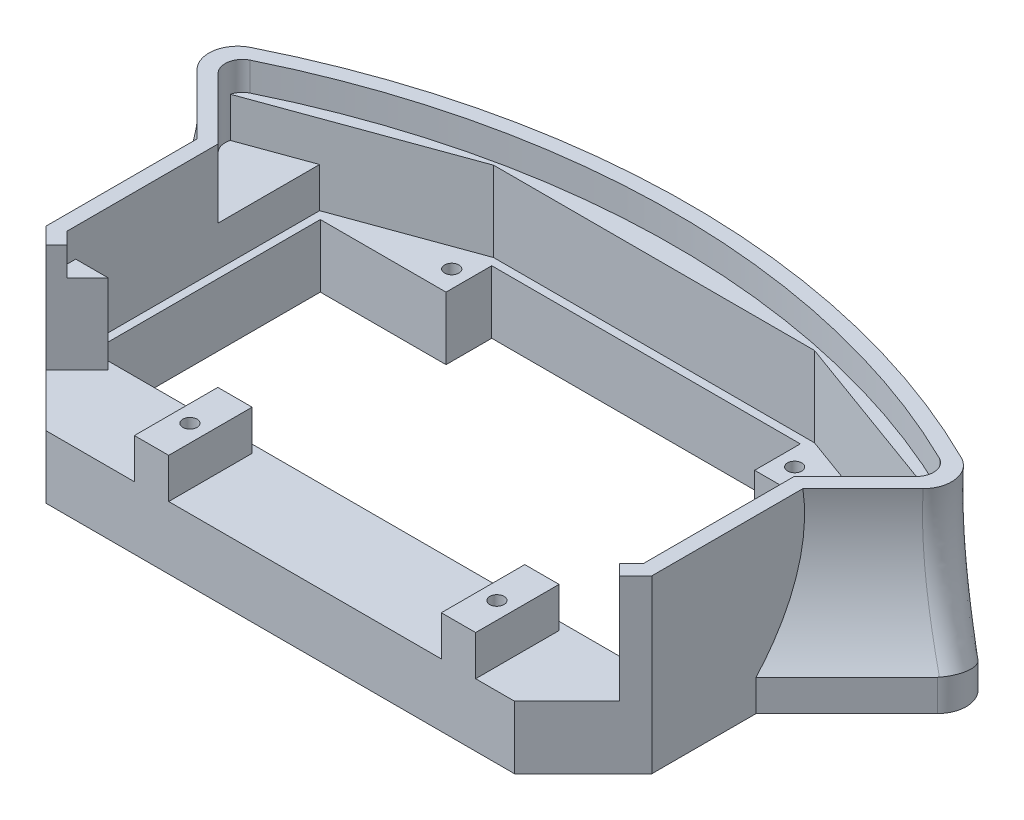
SolidWorks part; units mm, degrees
material "ABS"
ref_plane "Front Plane" through (0, 0, 0) normal (0, 0, 1) x (1, 0, 0)
ref_plane "Top Plane" through (0, 0, 0) normal (0, 1, 0) x (1, 0, 0)
ref_plane "Right Plane" through (0, 0, 0) normal (1, 0, 0) x (0, 0, -1)
sketch "Sketch1" plane through (0, 0, 0) normal (0, 1, 0) x (1, 0, 0)
  line L0 (53, 80) -> (53, 129.1478)
  line L1 (-53, 129.1478) -> (-53, 80)
  line L2 (-41, 68) -> (41, 68)
  line L3 (-53, 80) -> (-41, 68)
  line L4 (41, 68) -> (53, 80)
  circle A0 centre (0, 0) radius 140 construction
  arc A1 (53, 129.1478) -> (-53, 129.1478) centre (0, 0) ccw
  dimension "D1" = 280
  dimension "D3" = 139.6
  dimension "D2" = 106
  dimension "D4" = 68
  dimension "D5" = 80
  dimension "D6" = 135
  dimension "D7" = 135
extrude "Boss-Extrude1" add sketch "Sketch1" along normal blind 30
sketch "Sketch2" plane through (0, 30, 0) normal (0, 1, 0) x (1, 0, 0)
  line L0 (-49, 84) -> (49, 84)
  line L1 (49, 84) -> (49, 124)
  line L2 (49, 124) -> (27, 124)
  line L3 (27, 124) -> (27, 132)
  line L4 (27, 132) -> (-27, 132)
  line L5 (-27, 132) -> (-27, 124)
  line L6 (-27, 124) -> (-49, 124)
  line L7 (-49, 124) -> (-49, 84)
  line L12 (-53, 129.1478) -> (-53, 80) construction
  dimension "D1" = 48
  dimension "D2" = 98
  dimension "D3" = 8
  dimension "D4" = 84
  dimension "D5" = 22
  dimension "D6" = 4
extrude "Cut-Extrude1" cut sketch "Sketch2" against normal up to next
sketch "Sketch3" plane through (0, 30, 0) normal (0, 1, 0) x (1, 0, 0)
  line L0 (-50, 83) -> (50, 83) construction
  line L1 (50, 83) -> (50, 125) construction
  line L2 (50, 125) -> (28, 133) construction
  line L3 (28, 133) -> (-28, 133) construction
  line L4 (-28, 133) -> (-50, 125) construction
  line L5 (-50, 125) -> (-50, 83) construction
  line L7 (-49, 84) -> (-49, 124) construction
  line L8 (-50.4, 125.2802) -> (-50.4, 82.6)
  line L9 (-50.4, 82.6) -> (50.4, 82.6)
  line L10 (50.4, 82.6) -> (50.4, 125.2802)
  line L11 (50.4, 125.2802) -> (28.0705, 133.4)
  line L12 (28.0705, 133.4) -> (-28.0705, 133.4)
  line L13 (-28.0705, 133.4) -> (-50.4, 125.2802)
  line L16 (-49, 84) -> (49, 84) construction
  dimension "D1" = 50
  dimension "D2" = 22
  dimension "D3" = 8
  dimension "D4" = 1
  dimension "D5" = 1
  dimension "D6" = 100
  dimension "D7" = 0.4
extrude "Cut-Extrude2" cut sketch "Sketch3" against normal offset from surface (19 mm away) 11 up to face at (0, 0, -116)
sketch "Sketch5" plane through (0, 30, 0) normal (0, 1, 0) x (1, 0, 0)
  line L1 (-37.48, 71.91) -> (43.8, 71.91) construction
  line L2 (-37.48, 71.91) -> (-37.48, 125.25) construction
  line L3 (-37.48, 125.25) -> (43.8, 125.25) construction
  line L4 (43.8, 71.91) -> (43.8, 125.25) construction
  line L6 (-37.88, 71.51) -> (-37.88, 125.65)
  line L7 (-37.88, 125.65) -> (44.2, 125.65)
  line L8 (44.2, 71.51) -> (44.2, 125.65)
  line L9 (-37.88, 71.51) -> (44.2, 71.51)
  dimension "D1" = 71.91
  dimension "D2" = 43.8
  dimension "D3" = 81.28
  dimension "D4" = 53.34
  dimension "D5" = 0.4
extrude "Cut-Extrude4" cut sketch "Sketch5" against normal offset from surface (12 mm away) 18 up to face at (0, 0, -116)
sketch "Sketch4" plane through (0, 18, 0) normal (0, 1, 0) x (1, 0, 0)
  circle A0 centre (31.18, 74.72) radius 1.25
  circle A1 centre (-22.53, 74.72) radius 1.25
  dimension "D2" = 2.5
  dimension "D1" = 22.53
  dimension "D3" = 5.28
  dimension "D4" = 53.71
extrude "Cut-Extrude3" cut sketch "Sketch4" against normal up to next
fillet "Fillet1" radius 6 2 edges at (44.2, 24, -71.51) (-37.88, 24, -71.51)
sketch "Sketch6" plane through (0, 30, 0) normal (0, 1, 0) x (1, 0, 0)
  line L20 (50.4, 81.077) -> (50.4, 127.3925)
  line L21 (39.923, 70.6) -> (50.4, 81.077)
  line L22 (-39.923, 70.6) -> (39.923, 70.6)
  line L23 (-50.4, 81.077) -> (-39.923, 70.6)
  line L24 (-50.4, 127.3925) -> (-50.4, 81.077)
  line L25 (50.4, 81.077) -> (50.4, 127.3925)
  line L26 (39.923, 70.6) -> (50.4, 81.077)
  line L27 (-39.923, 70.6) -> (39.923, 70.6)
  line L28 (-50.4, 81.077) -> (-39.923, 70.6)
  line L29 (-50.4, 127.3925) -> (-50.4, 81.077)
  arc A7 (50.4, 127.3925) -> (-50.4, 127.3925) centre (0, 0) ccw
  arc A8 (50.4, 127.3925) -> (-50.4, 127.3925) centre (0, 0) ccw
  dimension "D1" = 2.6
extrude "Cut-Extrude5" cut sketch "Sketch6" against normal blind 5
sketch "Sketch7" plane through (0, 0, 0) normal (0, -1, 0) x (1, 0, 0)
  line L0 (73.4563, -118.7111) -> (53, -98.2548)
  line L1 (53, -80) -> (53, -129.1478) construction
  line L2 (53, -98.2548) -> (53, -129.1478)
  line L3 (0, 0) -> (103.3995, -103.3995) construction
  arc A0 (53, -129.1478) -> (73.4563, -118.7111) centre (0, 0) ccw
  arc A1 (-53, -129.1478) -> (53, -129.1478) centre (0, 0) ccw construction
  dimension "D1" = 45
  dimension "D2" = 32
extrude "Boss-Extrude2" add sketch "Sketch7" against normal up to surface (30 mm away) up to face at (0, 30, -94.6244)
ref_plane "Plane1" through (96.0837, 0, -96.0837) normal (-0.7071, 0, 0.7071) x (0, -1, 0)
sketch "Sketch8" plane through (96.0837, 0, -96.0837) normal (-0.7071, 0, 0.7071) x (0, -1, 0)
  line L0 (-30, -32) -> (0, -32) construction
  circle A0 centre (-26, 0) radius 38
  dimension "D3" = 76
  dimension "D1" = 32
  dimension "D2" = 26
extrude "Cut-Extrude6" cut sketch "Sketch8" along normal up to surface (98.9296 mm away) up to face at (53, 18.75, -84.5637)
mirror "Mirror1" about plane through (0, 0, 0) normal (1, 0, 0) of "Boss-Extrude2"
ref_plane "Plane2" through (-96.0837, 0, -96.0837) normal (0.7071, 0, 0.7071) x (0, -1, 0)
sketch "Sketch9" plane through (-96.0837, 0, -96.0837) normal (0.7071, 0, 0.7071) x (0, -1, 0)
  line L0 (-30, 32) -> (0, 32) construction
  circle A0 centre (-26, 0) radius 38
  dimension "D1" = 76
  dimension "D2" = 32
  dimension "D3" = 26
extrude "Cut-Extrude7" cut sketch "Sketch9" along normal up to surface (22.9296 mm away) up to face at (-53, 18.75, -93.6911)
fillet "Fillet2" radius 5 4 edges at (69.0949, 16.9868, -121.3015) (73.4563, 2.753, -118.7111) (-73.4563, 2.753, -118.7111) (-68.9598, 17.6248, -121.3784)
sketch "Sketch11" plane through (0, 11, 0) normal (0, 1, 0) x (1, 0, 0)
  line L0 (-49, 124) -> (-27, 124) construction
  circle A0 centre (-30, 128) radius 1.25
  circle A1 centre (30, 128) radius 1.25
  dimension "D2" = 2.5
  dimension "D1" = 4
  dimension "D3" = 60
  dimension "D4" = 30
extrude "Cut-Extrude9" cut sketch "Sketch11" against normal up to next
sketch "Sketch12" plane through (0, 30, 0) normal (0, 1, 0) x (1, 0, 0)
  line L0 (-61.0884, 118.2069) -> (-50.4, 107.5185)
  line L1 (-50.4, 127.3925) -> (-50.4, 81.077) construction
  line L2 (-50.4, 107.5185) -> (-50.4, 127.3925)
  line L3 (-63.5251, 116.9667) -> (-53, 106.4416) construction
  arc A0 (-50.4, 127.3925) -> (-60.2872, 123.0221) centre (0, 0) ccw
  arc A1 (-60.2872, 123.0221) -> (-61.0884, 118.2069) centre (-58.9671, 120.3282) ccw
  arc A3 (62.1871, 124.9837) -> (-62.1871, 124.9837) centre (0, 0) ccw construction
  dimension "D1" = 2.6
  dimension "D2" = 3
extrude "Cut-Extrude10" cut sketch "Sketch12" against normal up to surface (12 mm away) up to face at (-22.53, 18, -73.47)
sketch "Sketch14" plane through (0, 18, 0) normal (0, 1, 0) x (1, 0, 0)
  line L0 (-50.4, 127.3925) -> (-61.8629, 123.2241)
  line L1 (-61.8629, 123.2241) -> (-61.8629, 121.1118)
  line L2 (-61.8629, 121.1118) -> (-50.4, 125.2802)
  line L3 (-50.4, 125.2802) -> (-50.4, 127.3925)
  line L4 (-50.4, 125.2802) -> (-28.0705, 133.4) construction
  arc A0 (-60.2872, 123.0221) -> (-61.0884, 118.2069) centre (-58.9671, 120.3282) ccw construction
extrude "Boss-Extrude3" add sketch "Sketch14" along normal up to surface (7 mm away) up to face at (0, 25, -130.2921)
mirror "Mirror2" about plane through (0, 0, 0) normal (1, 0, 0) of "Boss-Extrude3", "Cut-Extrude10"
sketch "Sketch15" plane through (0, 30, 0) normal (0, 1, 0) x (1, 0, 0)
  line L0 (-50.1716, 77.1716) -> (-43.3431, 84)
  line L1 (-53, 80) -> (-41, 68) construction
  line L2 (49, 84) -> (-49, 84) construction
  line L3 (-43.3431, 84) -> (43.3431, 84)
  line L4 (43.3431, 84) -> (50.1716, 77.1716)
  line L5 (41, 68) -> (53, 80) construction
  line L6 (50.1716, 77.1716) -> (41, 68)
  line L7 (41, 68) -> (-41, 68)
  line L8 (-41, 68) -> (-50.1716, 77.1716)
  dimension "D1" = 4
  dimension "D2" = 4
extrude "Cut-Extrude12" cut sketch "Sketch15" against normal up to surface (12 mm away) up to face at (-22.53, 18, -73.47)
sketch "Sketch16" plane through (0, 18, 0) normal (0, 1, 0) x (1, 0, 0)
  line L0 (-50.1716, 77.1716) -> (-44.7431, 82.6)
  line L1 (-44.7431, 82.6) -> (-25.53, 82.6)
  line L2 (50.4, 82.6) -> (-50.4, 82.6) construction
  line L3 (-25.53, 82.6) -> (-25.53, 68)
  line L4 (41, 68) -> (-41, 68) construction
  line L5 (-25.53, 68) -> (-41, 68)
  line L6 (-41, 68) -> (-50.1716, 77.1716) construction
  line L7 (-41, 68) -> (-50.1716, 77.1716)
  line L8 (44.7431, 82.6) -> (-44.7431, 82.6) construction
  line L9 (-19.53, 68) -> (28.18, 68)
  line L10 (-19.53, 68) -> (-19.53, 82.6)
  line L11 (-19.53, 82.6) -> (28.18, 82.6)
  line L12 (28.18, 68) -> (28.18, 82.6)
  line L13 (34.18, 82.6) -> (34.18, 68)
  line L14 (34.18, 68) -> (41, 68)
  line L15 (41, 68) -> (50.1716, 77.1716)
  line L16 (50.1716, 77.1716) -> (44.7431, 82.6)
  line L17 (44.7431, 82.6) -> (34.18, 82.6)
  circle A0 centre (31.18, 74.72) radius 1.25 construction
  circle A3 centre (-22.53, 74.72) radius 1.25 construction
  dimension "D1" = 3
  dimension "D2" = 3
  dimension "D3" = 3
  dimension "D4" = 3
extrude "Cut-Extrude13" cut sketch "Sketch16" against normal up to surface (7 mm away) up to face at (30, 11, -126.75)
sketch "Sketch17" plane through (0, 0, 0) normal (0, -1, 0) x (1, 0, 0)
  circle A0 centre (-55, -115) radius 1.25
  circle A1 centre (55, -115) radius 1.25
  dimension "D1" = 2.5
  dimension "D2" = 115
  dimension "D3" = 55
  dimension "D4" = 55
extrude "Cut-Extrude14" cut sketch "Sketch17" against normal blind 12
